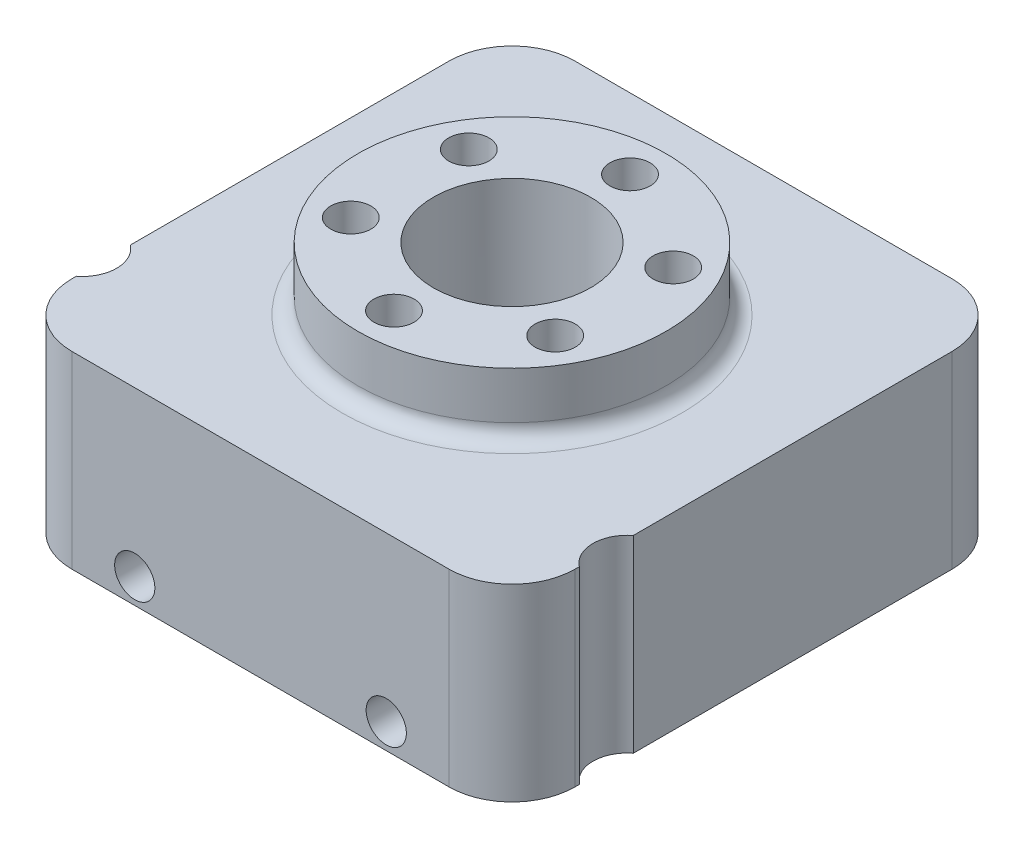
SolidWorks part; units mm, degrees
ref_plane "Front Plane" through (0, 0, 0) normal (0, 0, 1) x (1, 0, 0)
ref_plane "Top Plane" through (0, 0, 0) normal (0, 1, 0) x (1, 0, 0)
ref_plane "Right Plane" through (0, 0, 0) normal (1, 0, 0) x (0, 0, -1)
sketch "Sketch1" plane through (0, 0, 0) normal (0, 1, 0) x (1, 0, 0)
  line L0 (0, 0) -> (0, 35.4208) construction
  line L1 (-20, -20) -> (20, -20)
  line L2 (-20, -20) -> (-20, 20)
  line L3 (-20, 20) -> (20, 20)
  line L4 (20, -20) -> (20, 20)
  line L5 (-20, -20) -> (20, 20) construction
  line L6 (-20, 20) -> (20, -20) construction
  circle A0 centre (0, 0) radius 6.25
  circle A1 centre (0, 25) radius 2.7073
  circle A2 centre (21.6506, -12.5) radius 2.7073
  circle A3 centre (-21.6506, -12.5) radius 2.7073
  point P0 (0, 0)
  point P18 (0, 0)
  dimension "D2" = 12.5
  dimension "D1" = 25
  dimension "D3" = 40
  dimension "D4" = 40
  dimension "D5" = 3
extrude "Boss-Extrude1" add sketch "Sketch1" along normal blind 15 contours A3 L2 L1 L4 A2 L3 A0 region at (-19.4343, 0, 17.3229)
sketch "Sketch7" plane through (0, 15, 0) normal (0, 1, 0) x (1, 0, 0)
  circle A0 centre (0, 0) radius 12.25
  circle A1 centre (0, 0) radius 6.25
  dimension "D1" = 24.5
  dimension "D2" = 12.5
extrude "Boss-Extrude2" add sketch "Sketch7" along normal blind 5
fillet "Fillet1" radius 1.25 1 edges at (0, 15, 12.25)
sketch "Sketch5" plane through (0, 0, 0) normal (1, 0, 0) x (0, 0, -1)
  line L0 (4.8229, 15) -> (-4.8229, 0) construction
  line L1 (10, 5) -> (-10, 5)
  line L2 (10, 5) -> (10, 10)
  line L3 (10, 10) -> (-10, 10)
  line L4 (-10, 5) -> (-10, 10)
  line L5 (10, 5) -> (-10, 10) construction
  line L6 (10, 10) -> (-10, 5) construction
  line L7 (20, 7.5) -> (-20, 7.5) construction
  line L8 (20, 15) -> (20, 0) construction
  line L9 (-20, 15) -> (-20, 0) construction
  line L10 (-10.3541, 15) -> (20, 15) construction
  line L11 (-10.3541, 0) -> (20, 0) construction
  point P0 (0, 7.5)
  dimension "D1" = 20
  dimension "D2" = 5
extrude "Square side-insert" [suppressed] cut sketch "Sketch5" against normal up to surface (20 mm away) up to face at (-20, 7.5, -4.8229)
sketch "Sketch3" plane through (0, 0, -20) normal (0, 0, -1) x (-1, 0, 0)
  line L3 (0, 15) -> (0, 3) construction
  line L4 (20, 15) -> (-20, 15) construction
  circle A0 centre (0, 3) radius 1.6
  dimension "D2" = 3.2
  dimension "D1" = 12
extrude "Single Screw" cut sketch "Sketch3" against normal blind 17
sketch "Sketch2" plane through (0, 0, 20) normal (0, 0, 1) x (1, 0, 0)
  line L0 (0, 27.8717) -> (0, -11.9207) construction
  line L1 (20, 2) -> (10, 2)
  line L3 (10, 2) -> (10, 0)
  line L4 (-20, 0) -> (20, 0) construction
  line L5 (20, 15) -> (20, 0) construction
  circle A0 centre (10, 2) radius 1.6
  circle A1 centre (-10, 2) radius 1.6
  dimension "D3" = 3.2
  dimension "D1" = 10
  dimension "D2" = 2
extrude "Double Screw" cut sketch "Sketch2" against normal blind 10 contours A1 | A0
sketch "Sketch6" plane through (0, 20, 0) normal (0, 1, 0) x (1, 0, 0)
  circle A9 centre (0, -9.385) radius 1.6
  circle A10 centre (-8.1276, -4.6925) radius 1.6
  circle A11 centre (-8.1276, 4.6925) radius 1.6
  circle A12 centre (0, 9.385) radius 1.6
  circle A13 centre (8.1276, 4.6925) radius 1.6
  circle A14 centre (8.1276, -4.6925) radius 1.6
  point P3 (0, 0)
  point P16 (0, 0)
  dimension "D2" = 9.385
  dimension "D1" = 3.2
  dimension "D3" = 9.385
extrude "Cut-Extrude1" cut sketch "Sketch6" against normal through all
sketch "Sketch8" plane through (0, 15, 0) normal (0, 1, 0) x (1, 0, 0)
  line L0 (-20, 5) -> (-20, -5)
  line L1 (-20, -5) -> (-3.75, -5) construction
  line L2 (-20, 5) -> (-3.75, 5) construction
  line L3 (-20, -10.3541) -> (-20, 20) construction
  line L4 (-20, 5) -> (-20, 12.5)
  line L6 (-20, -5) -> (-20, -12.5)
  line L8 (-20, 12.5) -> (-13.9645, 6.4645)
  line L9 (-10.4289, 5) -> (-3.75, 5)
  line L10 (-20, -12.5) -> (-13.9645, -6.4645)
  line L11 (-10.4289, -5) -> (-3.75, -5)
  circle A0 centre (0, 0) radius 6.25 construction
  arc A1 (-3.75, 5) -> (-3.75, -5) centre (0, 0) ccw
  arc A2 (-13.9645, -6.4645) -> (-10.4289, -5) centre (-10.4289, -10) cw
  arc A3 (-10.4289, 5) -> (-13.9645, 6.4645) centre (-10.4289, 10) cw
  point P6 (-20, 0)
  point P8 (-12.7627, -8.5254)
  point P15 (0, 0)
  point P19 (-12.5, -5)
  point P22 (-12.5, 5)
  dimension "D2" = 7.5
  dimension "D5" = 5
  dimension "D1" = 10
  dimension "D3" = 7.5
  dimension "D4" = 7.5
extrude "Cut-Extrude3" cut sketch "Sketch8" against normal blind 5 from offset 5 offset against normal yes
fillet "Fillet2" radius 5 4 edges at (20, 7.5, 20) (20, 7.5, -20) (-20, 7.5, -20) (-20, 7.5, 20)
